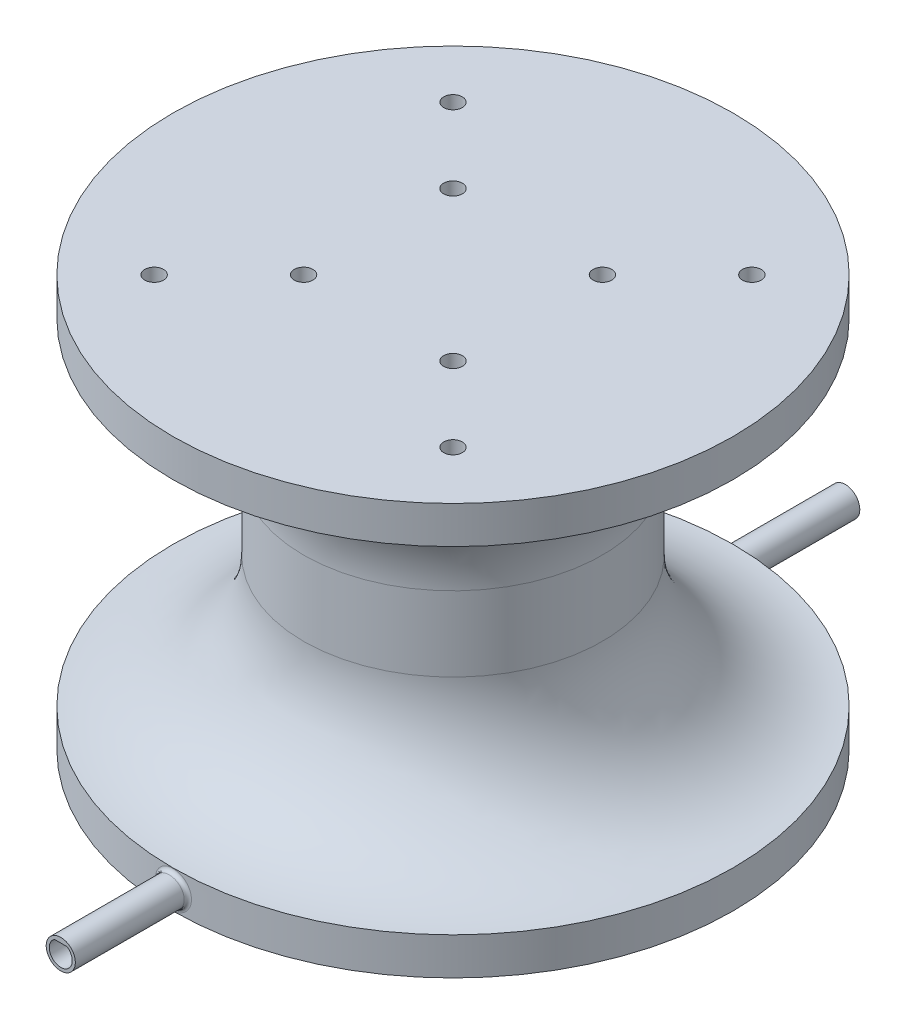
SolidWorks part; units mm, degrees
ref_plane "Front Plane" through (0, 0, 0) normal (0, 0, 1) x (1, 0, 0)
ref_plane "Top Plane" through (0, 0, 0) normal (0, 1, 0) x (1, 0, 0)
ref_plane "Right Plane" through (0, 0, 0) normal (1, 0, 0) x (0, 0, -1)
sketch "Sketch1" plane through (0, 0, 0) normal (0, 1, 0) x (1, 0, 0)
  circle A0 centre (0, 0) radius 75
  dimension "D1" = 150
extrude "Boss-Extrude1" add sketch "Sketch1" along normal blind 10
sketch "Sketch2" plane through (0, 0, 0) normal (0, 0, 1) x (1, 0, 0)
  circle A0 centre (0, 5) radius 3.9
  dimension "D1" = 5
  dimension "D2" = 7.8
extrude "Boss-Extrude2" add sketch "Sketch2" along normal mid plane 210
sketch "Sketch3" plane through (0, 0, 105) normal (0, 0, 1) x (1, 0, 0)
  line L0 (0, 1.1) -> (0, 5) construction
  circle A5 centre (0, 5) radius 3.9 construction
  circle A6 centre (0, 5) radius 3.9 construction
  circle A7 centre (0, 5) radius 3.075
  dimension "D1" = 6.15
sketch "Sketch4" plane through (0, 0, 0) normal (0, -1, 0) x (1, 0, 0)
  line L1 (-14, -10) -> (14, -10)
  line L2 (-14, -10) -> (-14, 10)
  line L3 (-14, 10) -> (14, 10)
  line L4 (14, -10) -> (14, 10)
  line L5 (-14, -10) -> (14, 10) construction
  line L6 (-14, 10) -> (14, -10) construction
  point P0 (0, 0)
  dimension "D1" = 28
  dimension "D2" = 20
extrude "Boss-Extrude3" add sketch "Sketch4" along normal blind 15
sketch "Sketch5" plane through (0, -15, 0) normal (0, -1, 0) x (1, 0, 0)
  line L0 (-7.53, -5.12) -> (7.53, -5.12) construction
  line L1 (-7.53, -5.12) -> (-14, -5.12) construction
  line L2 (-14, 10) -> (-14, -10) construction
  line L3 (7.53, -5.12) -> (14, -5.12) construction
  line L4 (14, -10) -> (14, 10) construction
  line L5 (-7.53, -5.12) -> (-7.53, -10) construction
  line L6 (-14, -10) -> (14, -10) construction
  circle A0 centre (-7.53, -5.12) radius 1.4
  circle A1 centre (7.53, -5.12) radius 1.4
  dimension "D1" = 15.06
  dimension "D3" = 2.8
  dimension "D4" = 2.8
  dimension "D2" = 4.88
extrude "Cut-Extrude2" cut sketch "Sketch5" against normal blind 7
fillet "Fillet1" radius 1 1 edges at (3.7968, 5.8911, 74.9038)
fillet "Fillet2" radius 1 1 edges at (-0.8911, 1.2032, -74.9947)
extrude "Cut-Extrude3" cut sketch "Sketch3" against normal blind 12.1
sketch "Sketch6" plane through (0, 10, 0) normal (0, 1, 0) x (1, 0, 0)
  circle A0 centre (0, 0) radius 40
extrude "Boss-Extrude4" add sketch "Sketch6" along normal blind 90
fillet "Fillet3" radius 35 1 edges at (0, 10, 40)
sketch "Sketch7" plane through (0, 100, 0) normal (0, 1, 0) x (1, 0, 0)
  circle A0 centre (0, 0) radius 75
extrude "Boss-Extrude5" add sketch "Sketch7" along normal blind 10
fillet "Fillet5" radius 35 1 edges at (0, 100, 40)
sketch "Sketch8" plane through (0, 110, 0) normal (0, 1, 0) x (1, 0, 0)
  circle A0 centre (20, 20) radius 2.5
  circle A1 centre (-20, 20) radius 2.5
  circle A2 centre (-20, -20) radius 2.5
  circle A3 centre (20, -20) radius 2.5
  circle A4 centre (-40, 40) radius 2.5
  circle A5 centre (40, 40) radius 2.5
  circle A6 centre (40, -40) radius 2.5
  circle A7 centre (-40, -40) radius 2.5
  point P16 (0, 0)
  point P19 (24.8285, -27.1032)
  dimension "D9" = 5
  dimension "D10" = 5
  dimension "D11" = 5
  dimension "D12" = 5
  dimension "D14" = 20
  dimension "D2" = 20
  dimension "D3" = 20
  dimension "D4" = 20
  dimension "D5" = 20
  dimension "D6" = 20
  dimension "D7" = 20
  dimension "D8" = 20
  dimension "D13" = 20
  dimension "D15" = 20
  dimension "D16" = 20
  dimension "D17" = 20
  dimension "D18" = 20
  dimension "D19" = 20
  dimension "D20" = 20
  dimension "D21" = 20
extrude "Cut-Extrude4" cut sketch "Sketch8" against normal blind 14 and the other way through all
sketch "Sketch12" plane through (0, -15, 0) normal (0, -1, 0) x (-1, 0, 0)
  line L0 (14, -10) -> (-14, -10)
  line L3 (-14, -10) -> (-14, 0)
  line L4 (-14, 10) -> (-14, -10) construction
  line L5 (-14, 0) -> (14, 0)
  line L6 (14, -10) -> (14, 10) construction
  line L7 (14, 0) -> (14, -10)
extrude "Cut-Extrude7" cut sketch "Sketch12" against normal blind 15
sketch "Sketch13" plane through (0, 0, 0) normal (0, 0, 1) x (1, 0, 0)
  line L0 (-12, 0) -> (-12, -13)
  line L1 (-14, 0) -> (14, 0) construction
  line L2 (-12, -13) -> (12, -13)
  line L3 (12, -13) -> (12, 0)
  line L4 (-14, 0) -> (-14, -15) construction
  line L5 (14, 0) -> (14, -15) construction
  line L6 (-12, 0) -> (12, 0)
  dimension "D1" = 13
  dimension "D2" = 2
  dimension "D3" = 2
extrude "Cut-Extrude9" cut sketch "Sketch13" against normal blind 15
sketch "Sketch14" plane through (0, 0, 92.9) normal (0, 0, 1) x (1, 0, 0)
  line L0 (0, 8.075) -> (0, 7.575) construction
  line L1 (-1.6808, 7.575) -> (1.6808, 7.575)
  circle A0 centre (0, 5) radius 3.075 construction
  circle A1 centre (0, 5) radius 3.075 construction
  arc A2 (1.6808, 7.575) -> (-1.6808, 7.575) centre (0, 5) ccw
  point P10 (0, 7.575)
  dimension "D1" = 0.5
extrude "Boss-Extrude6" add sketch "Sketch14" along normal blind 12.1
